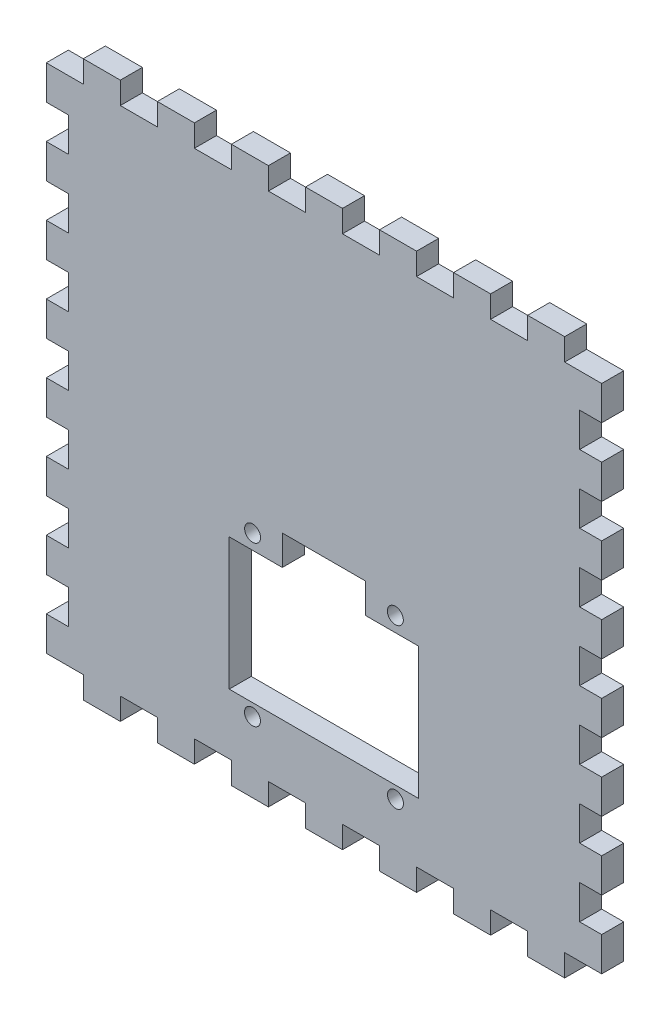
SolidWorks part; units mm, degrees
material "Acrylic (Medium-high impact)"
ref_plane "Front Plane" through (0, 0, 0) normal (0, 0, 1) x (1, 0, 0)
ref_plane "Top Plane" through (0, 0, 0) normal (0, 1, 0) x (1, 0, 0)
ref_plane "Right Plane" through (0, 0, 0) normal (1, 0, 0) x (0, 0, -1)
sketch "Sketch1" plane through (0, 0, 0) normal (0, 0, 1) x (1, 0, 0)
  line L1 (-40, -40) -> (40, -40)
  line L2 (-40, -40) -> (-40, 40)
  line L3 (-40, 40) -> (40, 40)
  line L4 (40, -40) -> (40, 40)
  line L5 (-40, -40) -> (40, 40) construction
  line L6 (-40, 40) -> (40, -40) construction
  point P0 (0, 0)
  dimension "D1" = 80
  dimension "D2" = 80
extrude "Boss-Extrude1" add sketch "Sketch1" along normal blind 3.175
sketch "Sketch2" plane through (0, 0, 3.175) normal (0, 0, 1) x (1, 0, 0)
  line L0 (0, 0) -> (-50000, 0) construction
  line L1 (-40, 40) -> (-40, -40) construction
  line L2 (-40, -36.825) -> (-34.6667, -36.825)
  line L3 (-34.6667, -36.825) -> (-34.6667, -40)
  line L5 (-40, 36.825) -> (-34.6667, 36.825)
  line L6 (-40, -36.825) -> (-40, -40)
  line L7 (-40, -40) -> (-34.6667, -40)
  line L8 (-34.6667, -40) -> (-40, -40)
  line L9 (-34.6667, -40) -> (-40, -40)
  line L10 (-29.3333, -36.825) -> (-29.3333, -40)
  line L11 (-29.3333, -36.825) -> (-24, -36.825)
  line L13 (-24, -36.825) -> (-24, -40)
  line L15 (-18.6667, -36.825) -> (-18.6667, -40)
  line L16 (-18.6667, -36.825) -> (-13.3333, -36.825)
  line L17 (-18.6667, -40) -> (-13.3333, -40)
  line L18 (-13.3333, -36.825) -> (-13.3333, -40)
  line L20 (-8, -36.825) -> (-8, -40)
  line L21 (-8, -36.825) -> (-2.6667, -36.825)
  line L22 (-8, -40) -> (-2.6667, -40)
  line L23 (-2.6667, -36.825) -> (-2.6667, -40)
  line L25 (2.6667, -36.825) -> (2.6667, -40)
  line L26 (2.6667, -36.825) -> (8, -36.825)
  line L27 (2.6667, -40) -> (8, -40)
  line L28 (8, -36.825) -> (8, -40)
  line L29 (40, 36.825) -> (40, 40)
  line L30 (13.3333, -36.825) -> (13.3333, -40)
  line L31 (13.3333, -36.825) -> (18.6667, -36.825)
  line L32 (13.3333, -40) -> (18.6667, -40)
  line L33 (18.6667, -36.825) -> (18.6667, -40)
  line L34 (34.6667, 40) -> (40, 40)
  line L35 (24, -36.825) -> (24, -40)
  line L36 (24, -36.825) -> (29.3333, -36.825)
  line L37 (24, -40) -> (29.3333, -40)
  line L38 (29.3333, -36.825) -> (29.3333, -40)
  line L39 (34.6667, 36.825) -> (40, 36.825)
  line L40 (34.6667, -36.825) -> (34.6667, -40)
  line L41 (34.6667, -36.825) -> (40, -36.825)
  line L42 (34.6667, -40) -> (40, -40)
  line L43 (40, -36.825) -> (40, -40)
  line L44 (34.6667, 36.825) -> (34.6667, 40)
  line L45 (-40, -36.825) -> (-34.6667, -36.825)
  line L46 (29.3333, 36.825) -> (29.3333, 40)
  line L47 (24, 40) -> (29.3333, 40)
  line L49 (24, 36.825) -> (29.3333, 36.825)
  line L51 (24, 36.825) -> (24, 40)
  line L53 (18.6667, 36.825) -> (18.6667, 40)
  line L54 (13.3333, 40) -> (18.6667, 40)
  line L55 (13.3333, 36.825) -> (18.6667, 36.825)
  line L56 (13.3333, 36.825) -> (13.3333, 40)
  line L57 (8, 36.825) -> (8, 40)
  line L58 (2.6667, 40) -> (8, 40)
  line L59 (2.6667, 36.825) -> (8, 36.825)
  line L60 (40, -31.915) -> (40, -36.825)
  line L61 (-36.825, -31.915) -> (-40, -31.915)
  line L62 (-36.825, -27.005) -> (-36.825, -31.915)
  line L63 (-40, -27.005) -> (-36.825, -27.005)
  line L64 (-40, -22.095) -> (-40, -27.005)
  line L65 (-36.825, -22.095) -> (-40, -22.095)
  line L66 (-36.825, -17.185) -> (-36.825, -22.095)
  line L68 (2.6667, 36.825) -> (2.6667, 40)
  line L69 (-2.6667, 36.825) -> (-2.6667, 40)
  line L70 (-8, 40) -> (-2.6667, 40)
  line L71 (-8, 36.825) -> (-2.6667, 36.825)
  line L72 (-8, 36.825) -> (-8, 40)
  line L73 (-13.3333, 36.825) -> (-13.3333, 40)
  line L74 (-18.6667, 40) -> (-13.3333, 40)
  line L75 (-18.6667, 36.825) -> (-13.3333, 36.825)
  line L76 (-18.6667, 36.825) -> (-18.6667, 40)
  line L77 (-24, 36.825) -> (-24, 40)
  line L78 (-29.3333, 36.825) -> (-24, 36.825)
  line L79 (-29.3333, 36.825) -> (-29.3333, 40)
  line L80 (-34.6667, 40) -> (-40, 40)
  line L81 (-34.6667, 40) -> (-40, 40)
  line L82 (-40, 40) -> (-34.6667, 40)
  line L83 (-40, 36.825) -> (-40, 40)
  line L84 (-34.6667, 36.825) -> (-34.6667, 40)
  line L85 (-40, 36.825) -> (-34.6667, 36.825)
  line L86 (40, 36.825) -> (40, 31.915)
  line L88 (40, 31.915) -> (36.825, 31.915)
  line L89 (36.825, 31.915) -> (36.825, 27.005)
  line L90 (36.825, 27.005) -> (40, 27.005)
  line L91 (40, 27.005) -> (40, 22.095)
  line L92 (40, 22.095) -> (36.825, 22.095)
  line L93 (36.825, 22.095) -> (36.825, 17.185)
  line L94 (36.825, 17.185) -> (40, 17.185)
  line L95 (40, 17.185) -> (40, 12.275)
  line L96 (40, 12.275) -> (36.825, 12.275)
  line L97 (36.825, 12.275) -> (36.825, 7.365)
  line L98 (36.825, 7.365) -> (40, 7.365)
  line L99 (40, 7.365) -> (40, 2.455)
  line L100 (40, 2.455) -> (36.825, 2.455)
  line L101 (36.825, 2.455) -> (36.825, -2.455)
  line L102 (36.825, -2.455) -> (40, -2.455)
  line L103 (40, -2.455) -> (40, -7.365)
  line L104 (40, -7.365) -> (36.825, -7.365)
  line L105 (36.825, -7.365) -> (36.825, -12.275)
  line L106 (36.825, -12.275) -> (40, -12.275)
  line L107 (40, -12.275) -> (40, -17.185)
  line L108 (40, -17.185) -> (36.825, -17.185)
  line L109 (36.825, -17.185) -> (36.825, -22.095)
  line L110 (36.825, -22.095) -> (40, -22.095)
  line L111 (40, -22.095) -> (40, -27.005)
  line L112 (40, -27.005) -> (36.825, -27.005)
  line L113 (36.825, -27.005) -> (36.825, -31.915)
  line L114 (36.825, -31.915) -> (40, -31.915)
  line L115 (0, 0) -> (0, 50000) construction
  line L116 (-40, 40) -> (-40, -40) construction
  line L117 (40, 40) -> (-40, 40) construction
  line L118 (-40, -17.185) -> (-36.825, -17.185)
  line L119 (-40, -12.275) -> (-40, -17.185)
  line L120 (-36.825, -12.275) -> (-40, -12.275)
  line L121 (-36.825, -7.365) -> (-36.825, -12.275)
  line L122 (-40, -7.365) -> (-36.825, -7.365)
  line L123 (-40, -2.455) -> (-40, -7.365)
  line L124 (-36.825, -2.455) -> (-40, -2.455)
  line L125 (-36.825, 2.455) -> (-36.825, -2.455)
  line L126 (-40, 2.455) -> (-36.825, 2.455)
  line L127 (-40, 7.365) -> (-40, 2.455)
  line L128 (-36.825, 7.365) -> (-40, 7.365)
  line L129 (-36.825, 12.275) -> (-36.825, 7.365)
  line L130 (-40, 12.275) -> (-36.825, 12.275)
  line L131 (-40, 17.185) -> (-40, 12.275)
  line L132 (-36.825, 17.185) -> (-40, 17.185)
  line L133 (-36.825, 22.095) -> (-36.825, 17.185)
  line L134 (-40, 22.095) -> (-36.825, 22.095)
  line L135 (-40, 27.005) -> (-40, 22.095)
  line L136 (-36.825, 27.005) -> (-40, 27.005)
  line L137 (-36.825, 31.915) -> (-36.825, 27.005)
  line L138 (-40, 31.915) -> (-36.825, 31.915)
  line L139 (-40, 36.825) -> (-40, 31.915)
  line L140 (-40, -31.915) -> (-40, -36.825)
  line L141 (34.6667, 40) -> (29.3333, 40)
  line L142 (24, 40) -> (18.6667, 40)
  line L143 (13.3333, 40) -> (8, 40)
  line L144 (2.6667, 40) -> (-2.6667, 40)
  line L145 (-8, 40) -> (-13.3333, 40)
  line L146 (-18.6667, 40) -> (-24, 40)
  line L147 (-29.3333, 40) -> (-34.6667, 40)
  point P111 (0, 40)
  line M50 (-40, 40) -> (-40, -40)
  line M51 (-40, -40) -> (40, -40)
  dimension "D2" = 3.175
  dimension "D5" = 3.175
extrude "Cut-Extrude1" cut sketch "Sketch2" against normal through all flip side to cut contours L138 L137 L136 L134 L133 L132 L130 L129 L128 L126 L125 L124 L122 L121 L120 L118 L66 L65 L63 L62 L61 L2 L3 L10 L11 L13 L15 L16 L18 L20 L21 L23 L25 L26 L28 L30 L31 L33 M50 M51 region at (0, 0, 3.175)
sketch "Sketch3" plane through (0, 0, 0) normal (0, 0, -1) x (-1, 0, 0)
  line L0 (0, 0) -> (0, -50000) construction
  line L1 (2.6667, -40) -> (-2.6667, -40) construction
  line L2 (-2.6667, -36.825) -> (-8, -36.825) construction
  line L3 (-13.65, -31.825) -> (13.65, -31.825) construction
  line L4 (-13.65, -31.825) -> (-13.65, -4.825) construction
  line L5 (-13.65, -4.825) -> (13.65, -4.825) construction
  line L6 (13.65, -31.825) -> (13.65, -4.825) construction
  line L7 (-13.65, -31.825) -> (13.65, -4.825) construction
  line L8 (-13.65, -4.825) -> (13.65, -31.825) construction
  line L9 (6, -4.825) -> (6, -9.125)
  line L10 (6, -9.125) -> (13.65, -9.125)
  line L11 (13.65, -9.125) -> (13.65, -28.125)
  line L12 (13.65, -28.125) -> (-13.65, -28.125)
  line L13 (6, -4.825) -> (-6, -4.825)
  line L14 (-13.65, -9.125) -> (-13.65, -28.125)
  line L15 (-6, -9.125) -> (-13.65, -9.125)
  line L16 (-6, -4.825) -> (-6, -9.125)
  circle A0 centre (-10.28, -6.975) radius 1.15
  circle A1 centre (-10.3, -29.875) radius 1.15
  circle A2 centre (10.3, -29.875) radius 1.15
  circle A3 centre (10.28, -6.975) radius 1.15
  point P5 (0, -40)
  point P6 (0, -18.325)
  point P20 (0, -28.125)
  point P23 (0, -4.825)
  point P29 (-9.3398, -29.9247)
  dimension "D7" = 2.3
  dimension "D8" = 2.3
  dimension "D1" = 27
  dimension "D2" = 27.3
  dimension "D3" = 5
  dimension "D4" = 12
  dimension "D5" = 19
  dimension "D6" = 22.7
  dimension "D9" = 3.37
  dimension "D10" = 2.15
  dimension "D11" = 1.95
  dimension "D12" = 3.35
extrude "Cut-Extrude2" cut sketch "Sketch3" against normal through all
